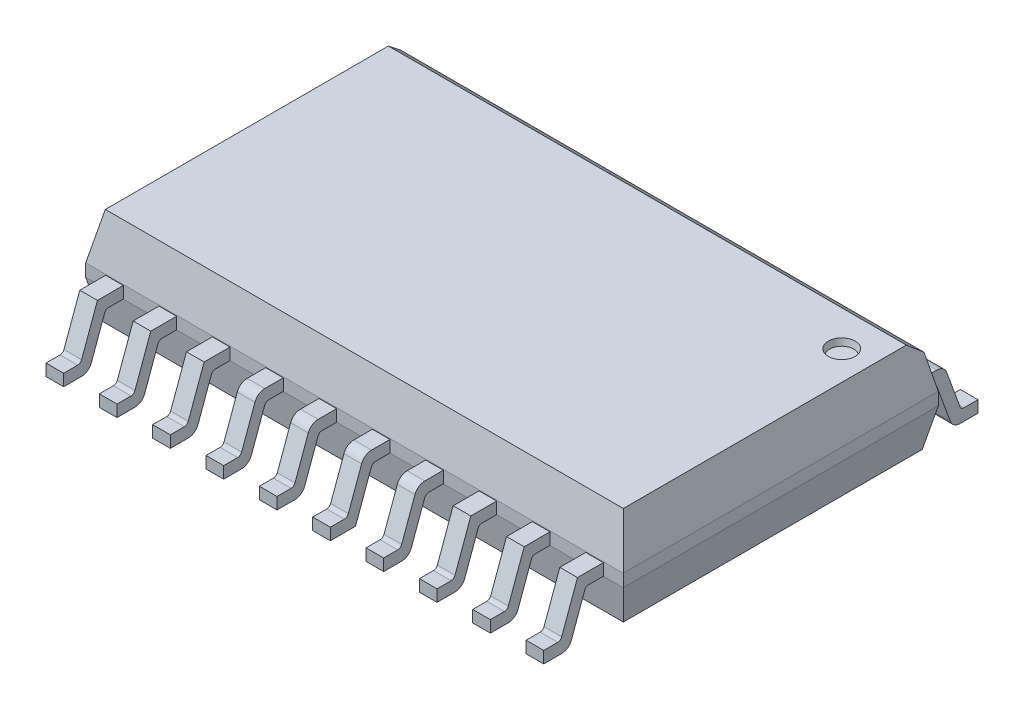
SolidWorks part; units mm, degrees
note: '?' marks a value the reader was unsure of.
ref_plane "Front Plane" through (0, 0, 0) normal (0, 0, 1) x (1, 0, 0)
ref_plane "Top Plane" through (0, 0, 0) normal (0, 1, 0) x (1, 0, 0)
ref_plane "Right Plane" through (0, 0, 0) normal (1, 0, 0) x (0, 0, -1)
ref_axis "Axis1" through (7.04, 0, 0) along (-1, 0, 0)?
sketch "Sketch1" plane through (0, 0, 0) normal (0, 1, 0) x (1, 0, 0)
  line L1 (-6.4, 3.75) -> (6.4, 3.75)
  line L2 (-6.4, 3.75) -> (-6.4, -3.75)
  line L3 (-6.4, -3.75) -> (6.4, -3.75)
  line L4 (6.4, 3.75) -> (6.4, -3.75)
  dimension "D1" = 12.8
  dimension "D2" = 7.5
  dimension "D3" = 6.4
  dimension "D4" = 3.75
extrude "Extrude1" add sketch "Sketch1" along normal blind 1.1 draft 12 and the other way blind 0.3
sketch "Sketch2" plane through (0, -0.3, 0) normal (0, -1, 0) x (1, 0, 0)
  line L4 (-6.4, 3.75) -> (-6.4, -3.75)
  line L5 (-6.4, -3.75) -> (6.4, -3.75)
  line L6 (6.4, -3.75) -> (6.4, 3.75)
  line L7 (6.4, 3.75) -> (-6.4, 3.75)
  line L8 (-6.4, 3.75) -> (-6.4, -3.75)
  line L9 (-6.4, -3.75) -> (6.4, -3.75)
  line L10 (6.4, -3.75) -> (6.4, 3.75)
  line L11 (6.4, 3.75) -> (-6.4, 3.75)
  dimension "D1" = 0
extrude "Extrude2" add sketch "Sketch2" along normal blind 0.9 draft 12
chamfer "Chamfer1" distance 0.3 angle 38.5 1 edges at (0, 1.1, -3.5162)
sketch "Sketch3" plane through (0, 1.1, 0) normal (0, 1, 0) x (-1, 0, 0)
  circle A0 centre (-5.473, -2.378) radius 0.3175
extrude "Cut-Extrude1" cut sketch "Sketch3" against normal blind 0.15 draft 12
sketch "Sketch4" plane through (0, 0, 0) normal (1, 0, 0) x (0, 0, -1)
  line L0 (0, -0.02) -> (0, -0.3)
  line L1 (-4.7661, -1.12) -> (-4.3657, -0.02)
  line L2 (-4.1696, -0.3) -> (4.1696, -0.3)
  line L3 (4.1696, -0.3) -> (4.57, -1.4)
  line L4 (-5.17, -1.12) -> (-4.7661, -1.12)
  line L5 (4.57, -1.4) -> (5.17, -1.4)
  line L6 (5.17, -1.4) -> (5.17, -1.12)
  line L7 (5.17, -1.12) -> (4.7661, -1.12)
  line L8 (4.7661, -1.12) -> (4.3657, -0.02)
  line L9 (4.3657, -0.02) -> (-4.3657, -0.02)
  line L10 (-5.17, -1.4) -> (-5.17, -1.12)
  line L11 (-4.57, -1.4) -> (-5.17, -1.4)
  line L12 (-4.1696, -0.3) -> (-4.57, -1.4)
  line L14 (-3.5587, -1.2) -> (3.5587, -1.2) construction
  line L15 (3.75, -0.3) -> (-3.75, -0.3) construction
  dimension "D1" = 0.28
  dimension "D2" = 0.28
  dimension "D3" = 0.28
  dimension "D4" = 0.6
  dimension "D5" = 10.34
  dimension "D6" = 110
  dimension "D7" = 0.2
extrude "Extrude3" add sketch "Sketch4" along normal blind 0.21 and the other way blind 0.21 from offset 0.635 contours L8 L9 L1 L4 L10 L11 L12 L2 L3 L5 L6 L7
pattern_linear "LPattern3" count 5 spacing 1.27 along (1, 0, 0) count 6 spacing 1.27 along (-1, 0, 0) of "Extrude3"
fillet "Fillet1" radius 0.1 40 edges at (1.905, -1.12, 4.7661) (0.635, -1.12, 4.7661) (-0.635, -1.12, 4.7661) (-1.905, -1.12, 4.7661) (1.905, -0.3, 4.1696) (0.635, -0.3, 4.1696) (-0.635, -0.3, 4.1696) (-1.905, -0.3, 4.1696) (1.905, -1.12, -4.7661) (0.635, -1.12, -4.7661) (-0.635, -1.12, -4.7661) (1.905, -0.3, -4.1696) (0.635, -0.3, -4.1696) (-0.635, -0.3, -4.1696) (-1.905, -0.3, -4.1696) (-1.905, -1.12, -4.7661) (5.715, -0.3, -4.1696) (4.445, -0.3, -4.1696) (3.175, -0.3, -4.1696) (-3.175, -0.3, -4.1696) (-4.445, -0.3, -4.1696) (-5.715, -0.3, -4.1696) (-5.715, -1.12, -4.7661) (-4.445, -1.12, -4.7661) (-3.175, -1.12, -4.7661) (5.715, -1.12, -4.7661) (4.445, -1.12, -4.7661) (3.175, -1.12, -4.7661) (-5.715, -1.12, 4.7661) (-4.445, -1.12, 4.7661) (-3.175, -1.12, 4.7661) (5.715, -1.12, 4.7661) (4.445, -1.12, 4.7661) (3.175, -1.12, 4.7661) (-5.715, -0.3, 4.1696) (-4.445, -0.3, 4.1696) (-3.175, -0.3, 4.1696) (5.715, -0.3, 4.1696) (4.445, -0.3, 4.1696) (3.175, -0.3, 4.1696)
fillet "Fillet2" radius 0.25 33 edges at (1.905, -1.4, 4.57) (1.905, -0.02, 4.3657) (-0.635, -0.02, 4.3657) (0.635, -0.02, 4.3657) (-0.635, -1.4, 4.57) (-1.905, -1.4, 4.57) (-1.905, -0.02, 4.3657) (1.905, -0.02, -4.3657) (0.635, -0.02, -4.3657) (-0.635, -0.02, -4.3657) (-1.905, -0.02, -4.3657) (1.905, -1.4, -4.57) (0.635, -1.4, -4.57) (-0.635, -1.4, -4.57) (-1.905, -1.4, -4.57) (-5.715, -1.4, 4.57) (-4.445, -1.4, 4.57) (-3.175, -1.4, 4.57) (5.715, -1.4, 4.57) (4.445, -1.4, 4.57) (3.175, -1.4, 4.57) (5.715, -1.4, -4.57) (4.445, -1.4, -4.57) (3.175, -1.4, -4.57) (-3.175, -1.4, -4.57) (-4.445, -1.4, -4.57) (-5.715, -1.4, -4.57) (5.715, -0.02, -4.3657) (4.445, -0.02, -4.3657) (3.175, -0.02, -4.3657) (-5.715, -0.02, -4.3657) (-4.445, -0.02, -4.3657) (-3.175, -0.02, -4.3657)
ref_plane "Plane1" through (0, -1.4, 0) normal (0, 1, 0) x (-1, 0, 0)
sketch "Component_Outline" plane through (0, -1.4, 0) normal (0, 1, 0) x (-1, 0, 0)
  line L0 (6.4, -3.75) -> (5.925, -3.75)
  line L1 (-1.695, -5.17) -> (-2.115, -5.17)
  line L2 (5.505, -5.17) -> (5.505, -3.75)
  line L3 (5.505, -3.75) -> (4.655, -3.75)
  line L4 (4.655, -5.17) -> (4.655, -3.75)
  line L5 (-4.235, -5.17) -> (-4.655, -5.17)
  line L6 (4.235, -5.17) -> (4.235, -3.75)
  line L7 (4.235, -3.75) -> (3.385, -3.75)
  line L8 (3.385, -5.17) -> (3.385, -3.75)
  line L9 (-5.505, -5.17) -> (-5.925, -5.17)
  line L10 (2.965, -5.17) -> (2.965, -3.75)
  line L11 (2.965, -3.75) -> (2.115, -3.75)
  line L12 (2.115, -5.17) -> (2.115, -3.75)
  line L13 (-6.4, 0) -> (6.4, 0) construction
  line L14 (1.695, -5.17) -> (1.695, -3.75)
  line L15 (1.695, -3.75) -> (0.845, -3.75)
  line L16 (0.845, -5.17) -> (0.845, -3.75)
  line L17 (-2.965, 5.17) -> (-3.385, 5.17)
  line L18 (0.425, -5.17) -> (0.425, -3.75)
  line L19 (0.425, -3.75) -> (-0.425, -3.75)
  line L20 (-0.425, -5.17) -> (-0.425, -3.75)
  line L21 (-6.4, -3.75) -> (-6.4, 3.75)
  line L22 (-0.845, -5.17) -> (-0.845, -3.75)
  line L23 (-0.845, -3.75) -> (-1.695, -3.75)
  line L24 (-1.695, -5.17) -> (-1.695, -3.75)
  line L26 (-2.115, -5.17) -> (-2.115, -3.75)
  line L27 (-2.115, -3.75) -> (-2.965, -3.75)
  line L28 (-2.965, -5.17) -> (-2.965, -3.75)
  line L30 (-3.385, -5.17) -> (-3.385, -3.75)
  line L31 (-3.385, -3.75) -> (-4.235, -3.75)
  line L32 (-4.235, -5.17) -> (-4.235, -3.75)
  line L34 (-4.655, -5.17) -> (-4.655, -3.75)
  line L35 (-4.655, -3.75) -> (-5.505, -3.75)
  line L36 (-5.505, -5.17) -> (-5.505, -3.75)
  line L37 (5.925, -3.75) -> (5.925, -5.17)
  line L38 (5.925, -5.17) -> (5.505, -5.17)
  line L39 (-5.925, -5.17) -> (-5.925, -3.75)
  line L40 (-5.925, -3.75) -> (-6.4, -3.75)
  line L41 (4.655, -5.17) -> (4.235, -5.17)
  line L42 (3.385, -5.17) -> (2.965, -5.17)
  line L43 (2.115, -5.17) -> (1.695, -5.17)
  line L44 (0.845, -5.17) -> (0.425, -5.17)
  line L45 (-0.425, -5.17) -> (-0.845, -5.17)
  line L46 (-2.965, -5.17) -> (-3.385, -5.17)
  line L47 (-6.4, 3.75) -> (-6.4, -3.75) construction
  line L48 (6.4, -3.75) -> (6.4, 3.75) construction
  line L50 (-0.425, 5.17) -> (-0.845, 5.17)
  line L51 (0.845, 5.17) -> (0.425, 5.17)
  line L52 (2.115, 5.17) -> (1.695, 5.17)
  line L53 (3.385, 5.17) -> (2.965, 5.17)
  line L54 (4.655, 5.17) -> (4.235, 5.17)
  line L55 (-5.925, 3.75) -> (-6.4, 3.75)
  line L56 (-5.925, 5.17) -> (-5.925, 3.75)
  line L57 (5.925, 5.17) -> (5.505, 5.17)
  line L58 (5.925, 3.75) -> (5.925, 5.17)
  line L59 (-5.505, 5.17) -> (-5.505, 3.75)
  line L60 (-4.655, 3.75) -> (-5.505, 3.75)
  line L61 (-4.655, 5.17) -> (-4.655, 3.75)
  line L62 (-4.235, 5.17) -> (-4.235, 3.75)
  line L63 (-3.385, 3.75) -> (-4.235, 3.75)
  line L64 (-3.385, 5.17) -> (-3.385, 3.75)
  line L65 (-2.965, 5.17) -> (-2.965, 3.75)
  line L66 (-2.115, 3.75) -> (-2.965, 3.75)
  line L67 (-2.115, 5.17) -> (-2.115, 3.75)
  line L68 (-1.695, 5.17) -> (-1.695, 3.75)
  line L69 (-0.845, 3.75) -> (-1.695, 3.75)
  line L70 (-0.845, 5.17) -> (-0.845, 3.75)
  line L71 (-0.425, 5.17) -> (-0.425, 3.75)
  line L72 (0.425, 3.75) -> (-0.425, 3.75)
  line L73 (0.425, 5.17) -> (0.425, 3.75)
  line L74 (0.845, 5.17) -> (0.845, 3.75)
  line L75 (1.695, 3.75) -> (0.845, 3.75)
  line L76 (1.695, 5.17) -> (1.695, 3.75)
  line L77 (2.115, 5.17) -> (2.115, 3.75)
  line L78 (2.965, 3.75) -> (2.115, 3.75)
  line L79 (2.965, 5.17) -> (2.965, 3.75)
  line L80 (-5.505, 5.17) -> (-5.925, 5.17)
  line L81 (3.385, 5.17) -> (3.385, 3.75)
  line L82 (4.235, 3.75) -> (3.385, 3.75)
  line L83 (4.235, 5.17) -> (4.235, 3.75)
  line L84 (-4.235, 5.17) -> (-4.655, 5.17)
  line L85 (4.655, 5.17) -> (4.655, 3.75)
  line L86 (5.505, 3.75) -> (4.655, 3.75)
  line L87 (5.505, 5.17) -> (5.505, 3.75)
  line L88 (-1.695, 5.17) -> (-2.115, 5.17)
  line L89 (6.4, 3.75) -> (5.925, 3.75)
  line L90 (6.4, -3.75) -> (6.4, 3.75)
  point P114 (0, 0)
